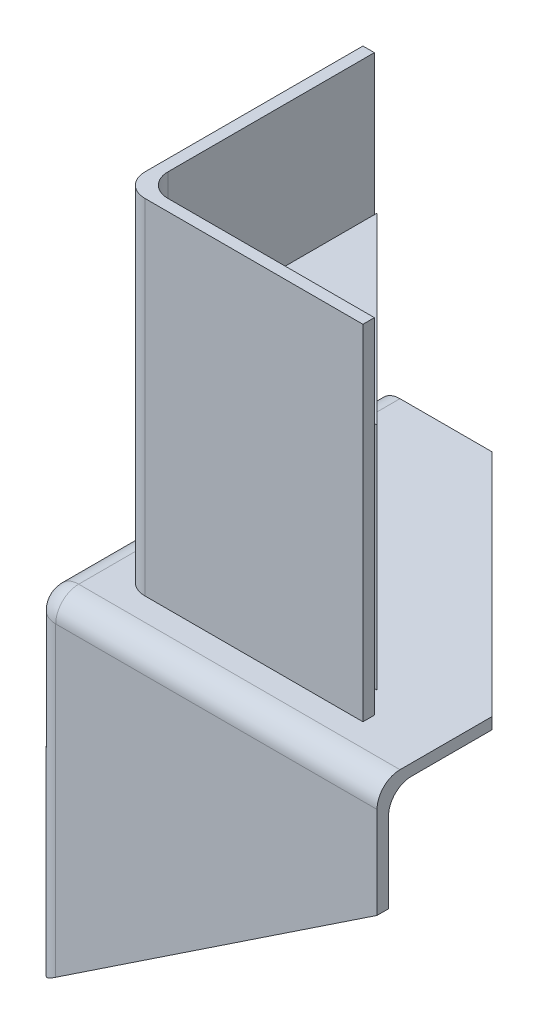
SolidWorks part; units mm, degrees
ref_plane "Front Plane" through (0, 0, 0) normal (0, 0, 1) x (1, 0, 0)
ref_plane "Top Plane" through (0, 0, 0) normal (0, 1, 0) x (1, 0, 0)
ref_plane "Right Plane" through (0, 0, 0) normal (1, 0, 0) x (0, 0, -1)
sketch "Sketch1" plane through (0, 0, 0) normal (0, 1, 0) x (1, 0, 0)
  line L0 (0, 0) -> (30, 0)
  line L1 (30, 0) -> (30, 10)
  line L2 (0, 0) -> (0, 30)
  line L3 (0, 30) -> (10, 30)
  line L4 (10, 30) -> (30, 10)
  line L5 (0, 0) -> (5.77, 0)
  line L6 (7, 7) -> (7, 23)
  line L7 (0, 0) -> (0, 7)
  line L8 (7, 7) -> (23, 7)
  line L9 (23, 7) -> (7, 23)
  line L10 (5.77, 0) -> (4.77, 0)
  line L11 (0, 30) -> (1, 30)
  line L12 (4.77, 0) -> (3.77, 0)
  line L13 (1, 30) -> (1, 1)
  line L14 (4.77, 5) -> (24.77, 5)
  line L15 (24.77, 5) -> (24.77, 4)
  line L16 (24.77, 4) -> (3.77, 4)
  line L17 (3.77, 4) -> (3.77, 25)
  line L18 (3.77, 25) -> (4.77, 25)
  line L19 (4.77, 25) -> (4.77, 5)
  line L20 (1, 1) -> (30, 1)
extrude "Boss-Extrude1" add sketch "Sketch1" against normal blind 30 contours L20 L13 L3 L2 L0 L5 L1 region at (0.4243, 0, -3.5)
extrude "Boss-Extrude2" add sketch "Sketch1<3>" against normal blind 1 contours L13 L20 L1 L4 L3 L18 L19 L14 L15 L16 L17 L9 L8 L6 region at (5.5, 0, -29.5899)
sketch "Sketch1<3>" plane through (0, 0, 0) normal (0, 1, 0) x (1, 0, 0) same geometry as "Sketch1"
extrude "Boss-Extrude3" add sketch "Sketch1<4>" along normal blind 20 and the other way blind 1 contours L8 L9 L6 region at (12.3333, 0, -12.3333)
sketch "Sketch1<4>" plane through (0, 0, 0) normal (0, 1, 0) x (1, 0, 0) same geometry as "Sketch1"
extrude "Boss-Extrude4" add sketch "Sketch1<5>" along normal blind 30 and the other way blind 1 contours L19 L18 L17 L16 L15 L14 region at (14.77, 0, -4.703)
sketch "Sketch1<5>" plane through (0, 0, 0) normal (0, 1, 0) x (1, 0, 0) same geometry as "Sketch1"
sketch "Sketch3" plane through (0, 0, 0) normal (0, 0, 1) x (1, 0, 0)
  line L1 (30, -30) -> (30, 0) construction
  line L2 (30, -10) -> (0, -30)
  line L3 (0, -30) -> (30, -30)
  line L4 (30, -30) -> (30, -10)
sketch "Sketch4" plane through (0, 0, 0) normal (1, 0, 0) x (0, 0, -1)
  line L1 (30, -30) -> (30, 0) construction
  line L2 (30, -10) -> (0, -30)
  line L3 (0, -30) -> (30, -30)
  line L4 (30, -30) -> (30, -10)
extrude "Cut-Extrude1" cut sketch "Sketch3" against normal blind 30
extrude "Cut-Extrude2" cut sketch "Sketch4" along normal blind 30
fillet "Fillet2" radius 2 4 edges at (4.77, 15, -5) (1, -15.1667, -1) (3.77, 15, -4) (0, -15, 0)
fillet "Fillet3" radius 2 6 edges at (0.5858, 0, -0.5858) (1.5858, -1, -1.5858) (0, 0, -16) (16, 0, 0) (16.5, -1, -1) (1, -1, -16.5)
